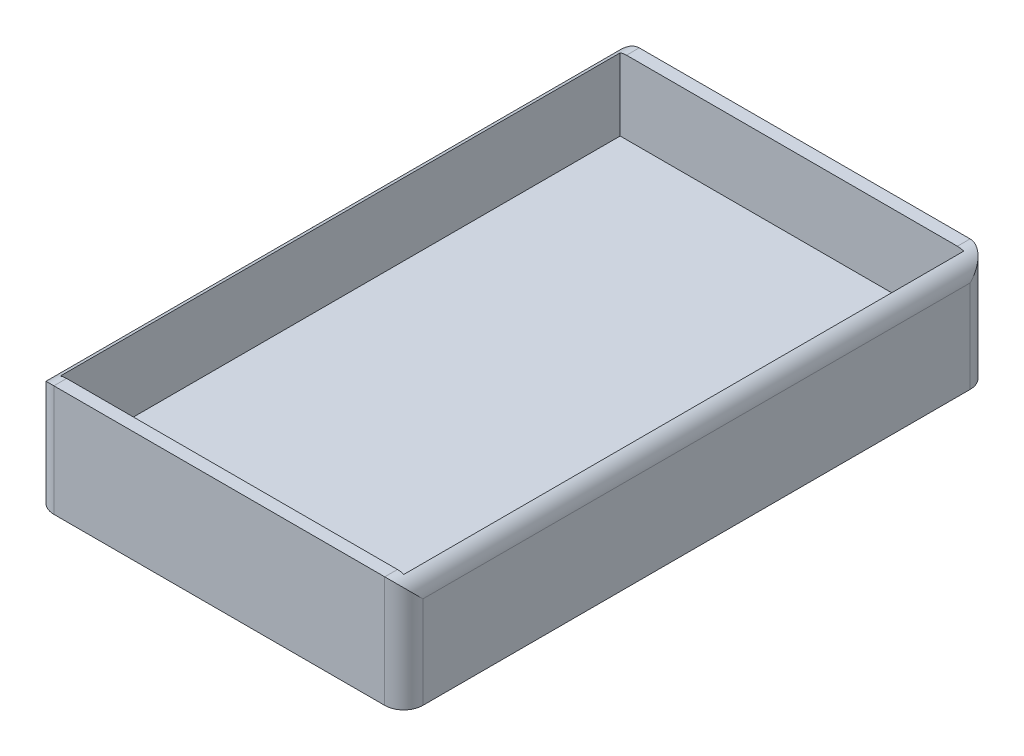
SolidWorks part; units mm, degrees
ref_plane "Front Plane" through (0, 0, 0) normal (0, 0, 1) x (1, 0, 0)
ref_plane "Top Plane" through (0, 0, 0) normal (0, 1, 0) x (1, 0, 0)
ref_plane "Right Plane" through (0, 0, 0) normal (1, 0, 0) x (0, 0, -1)
sketch "Sketch1" plane through (0, 0, 0) normal (0, 1, 0) x (1, 0, 0)
  line L1 (-29, -46) -> (29, -46)
  line L2 (-29, -46) -> (-29, 46)
  line L3 (-29, 46) -> (29, 46)
  line L4 (29, -46) -> (29, 46)
  line L5 (-29, -46) -> (29, 46) construction
  line L6 (-29, 46) -> (29, -46) construction
  point P0 (0, 0)
  dimension "D1" = 92
  dimension "D2" = 58
extrude "Boss-Extrude1" add sketch "Sketch1" along normal blind 17.5
sketch "Sketch2" plane through (0, 17.5, 0) normal (0, 1, 0) x (1, 0, 0)
  line L0 (-29, 46) -> (-29, -46) construction
  line L1 (-27, -44) -> (27, -44)
  line L2 (-27, -44) -> (-27, 44)
  line L3 (-27, 44) -> (27, 44)
  line L4 (27, -44) -> (27, 44)
  line L5 (-27, -44) -> (27, 44) construction
  line L6 (-27, 44) -> (27, -44) construction
  line L7 (29, 46) -> (-29, 46) construction
  point P0 (0, 0)
  dimension "D1" = 2
  dimension "D2" = 2
extrude "Cut-Extrude1" cut sketch "Sketch2" against normal blind 11.5
fillet "Fillet3" radius 3 6 edges at (29, 8.75, -46) (29, 17.5, 0) (29, 8.75, 46) (-29, 8.75, -46) (-29, 8.75, 46) (-29, 17.5, 0)
